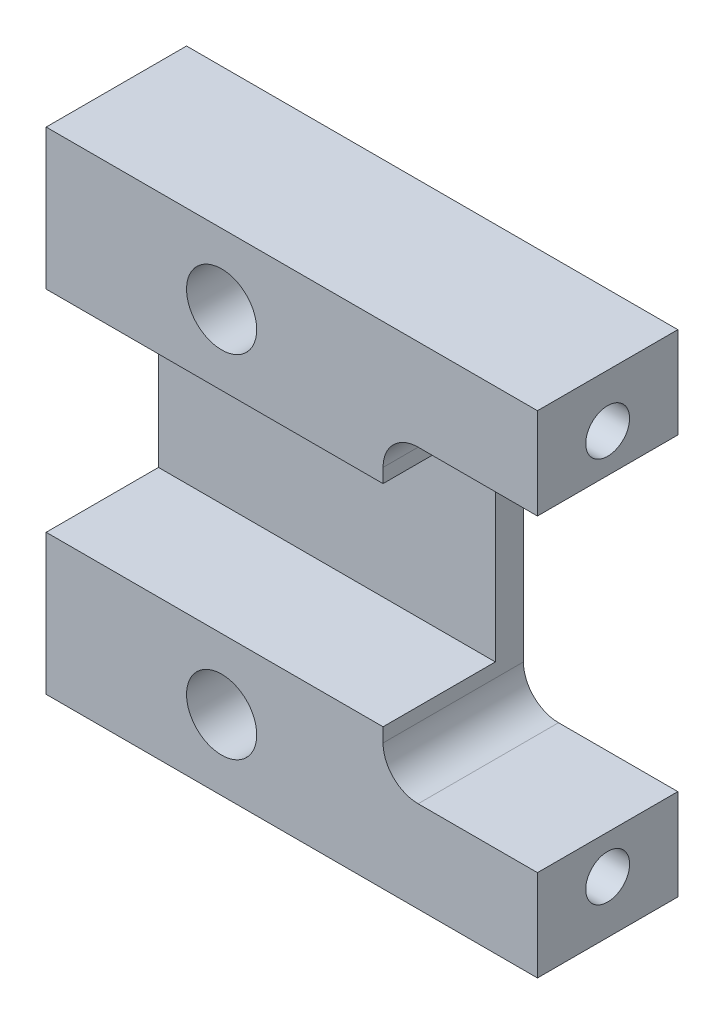
SolidWorks part; units mm, degrees
material "6061-T6 (SS)"
ref_plane "Front Plane" through (0, 0, 0) normal (0, 0, 1) x (1, 0, 0)
ref_plane "Top Plane" through (0, 0, 0) normal (0, 1, 0) x (1, 0, 0)
ref_plane "Right Plane" through (0, 0, 0) normal (1, 0, 0) x (0, 0, -1)
sketch "Sketch1" plane through (0, 0, 0) normal (0, 0, 1) x (1, 0, 0)
  line L1 (-44.45, -44.45) -> (44.45, -44.45)
  line L2 (-44.45, -44.45) -> (-44.45, 44.45)
  line L3 (-44.45, 44.45) -> (44.45, 44.45)
  line L4 (44.45, -44.45) -> (44.45, 44.45)
  line L5 (-44.45, -44.45) -> (44.45, 44.45) construction
  line L6 (-44.45, 44.45) -> (44.45, -44.45) construction
  point P0 (0, 0)
  dimension "D1" = 88.9
  dimension "D2" = 88.9
extrude "Extrude1" add sketch "Sketch1" along normal blind 25.4
sketch "Sketch2" plane through (44.45, 0, 0) normal (1, 0, 0) x (0, 0, -1)
  line L0 (-12.7, 44.45) -> (-12.7, 34.925) construction
  line L1 (-25.4, 44.45) -> (0, 44.45) construction
  dimension "D1" = 9.525
hole_wizard "Tap Drill for 3/8-16 Tap2" positions "Sketch4" profile "Sketch3" hole size "3/8-16" standard "Ansi Inch"
sketch "Sketch4" plane through (44.45, 0, 0) normal (1, 0, 0) x (0, 0, -1)
  point P1 (-12.7, 34.925)
sketch "Sketch3" plane through (44.45, 34.925, 12.7) normal (0, 1, 0) x (0, 0, -1)
  line L0 (0, 0) -> (0, 20.1647)
  line L1 (0, 20.1647) -> (3.9687, 17.78)
  line L2 (3.9687, 17.78) -> (3.9687, 0)
  line L5 (3.9687, 0) -> (0, 0)
  line L10 (0, 20.1647) -> (-3.9688, 17.78) construction
  line L11 (0, -6.35) -> (0, 107.95) construction
  dimension "Hole Dia." = 7.9375
  dimension "Hole Depth" = 17.78
  dimension "Drill Angle" = 118
mirror "Mirror1" about plane through (0, 0, 0) normal (0, 1, 0) of "Tap Drill for 3/8-16 Tap2"
sketch "Sketch5" plane through (0, 0, 25.4) normal (0, 0, 1) x (1, 0, 0)
  line L0 (-12.7, 44.45) -> (-12.7, 31.75) construction
  line L5 (44.45, 44.45) -> (-44.45, 44.45) construction
  line L6 (-44.45, 44.45) -> (-44.45, -44.45) construction
  dimension "D1" = 12.7
  dimension "D2" = 31.75
hole_wizard "1/2 (0.5) Diameter Hole1" positions "Sketch7" profile "Sketch6" hole size "1/2" standard "Ansi Inch" end condition through all
sketch "Sketch7" plane through (0, 0, 25.4) normal (0, 0, 1) x (1, 0, 0)
  point P6 (-12.7, 31.75)
sketch "Sketch6" plane through (-12.7, 31.75, 25.4) normal (1, 0, 0) x (0, -1, 0)
  line L0 (0, 0) -> (0, 25.4)
  line L1 (0, 25.4) -> (6.35, 25.4)
  line L2 (6.35, 25.4) -> (6.35, 0)
  line L5 (6.35, 0) -> (0, 0)
  line L11 (0, -6.35) -> (0, 107.95) construction
  dimension "Thru Hole Dia." = 12.7
  dimension "Thru Hole Depth" = 25.4
mirror "Mirror3" about plane through (0, 0, 0) normal (0, 1, 0) of "1/2 (0.5) Diameter Hole1"
sketch "Sketch15" plane through (0, 0, 25.4) normal (0, 0, 1) x (1, 0, 0)
  line L0 (-44.45, 0) -> (-44.45, 19.05)
  line L1 (-44.45, 44.45) -> (-44.45, -44.45) construction
  line L2 (-44.45, 19.05) -> (16.51, 19.05)
  line L3 (16.51, 19.05) -> (16.51, 27.94)
  line L4 (16.51, 27.94) -> (44.45, 27.94)
  line L5 (44.45, -44.45) -> (44.45, 44.45) construction
  line L6 (44.45, 27.94) -> (44.45, 0)
  line L7 (44.45, 0) -> (-44.45, 0)
  dimension "D1" = 19.05
  dimension "D2" = 27.94
  dimension "D3" = 27.94
extrude "Extrude5" cut sketch "Sketch15" against normal blind 20.32
mirror "Mirror4" about plane through (0, 0, 0) normal (0, 1, 0) of "Extrude5"
sketch "Sketch16" plane through (0, 0, 5.08) normal (0, 0, 1) x (1, 0, 0)
  line L1 (16.51, 27.94) -> (44.45, 27.94)
  line L2 (16.51, 27.94) -> (16.51, -27.94)
  line L3 (16.51, -27.94) -> (44.45, -27.94)
  line L4 (44.45, 27.94) -> (44.45, -27.94)
extrude "Extrude6" cut sketch "Sketch16" against normal through all
fillet "Fillet2" radius 6.35 2 edges at (16.51, -27.94, 12.7) (16.51, 27.94, 12.7)
sketch "Sketch17" plane through (-44.45, 0, 0) normal (-1, 0, 0) x (0, 0, 1)
  line L0 (12.7, 44.45) -> (12.7, 31.75) construction
  line L1 (25.4, 44.45) -> (0, 44.45) construction
  dimension "D1" = 12.7
hole_wizard "Tap Drill for 1/2-13 Tap2" positions "3DSketch1" profile "Sketch18" hole size "1/2-13" standard "Ansi Inch"
sketch3d "3DSketch1"
  point P0 (-44.45, 31.75, 12.7)
sketch "Sketch18" plane through (-44.45, 31.75, 12.7) normal (0, 1, 0) x (0, 0, 1)
  line L0 (0, 0) -> (0, 20.9995)
  line L1 (0, 20.9995) -> (5.3581, 17.78)
  line L2 (5.3581, 17.78) -> (5.3581, 0)
  line L5 (5.3581, 0) -> (0, 0)
  line L10 (0, 20.9995) -> (-5.3581, 17.78) construction
  line L11 (0, -6.35) -> (0, 107.95) construction
  dimension "Hole Dia." = 10.7163
  dimension "Hole Depth" = 17.78
  dimension "Drill Angle" = 118
mirror "Mirror5" about plane through (0, 0, 0) normal (0, 1, 0) of "Tap Drill for 1/2-13 Tap2"
ref_plane "Plane1" through (0, 0, 31.75) normal (0, 0, 1) x (1, 0, 0)
sketch "Sketch19" plane through (0, 0, 31.75) normal (0, 0, 1) x (1, 0, 0)
  point P0 (-44.45, -44.45)
